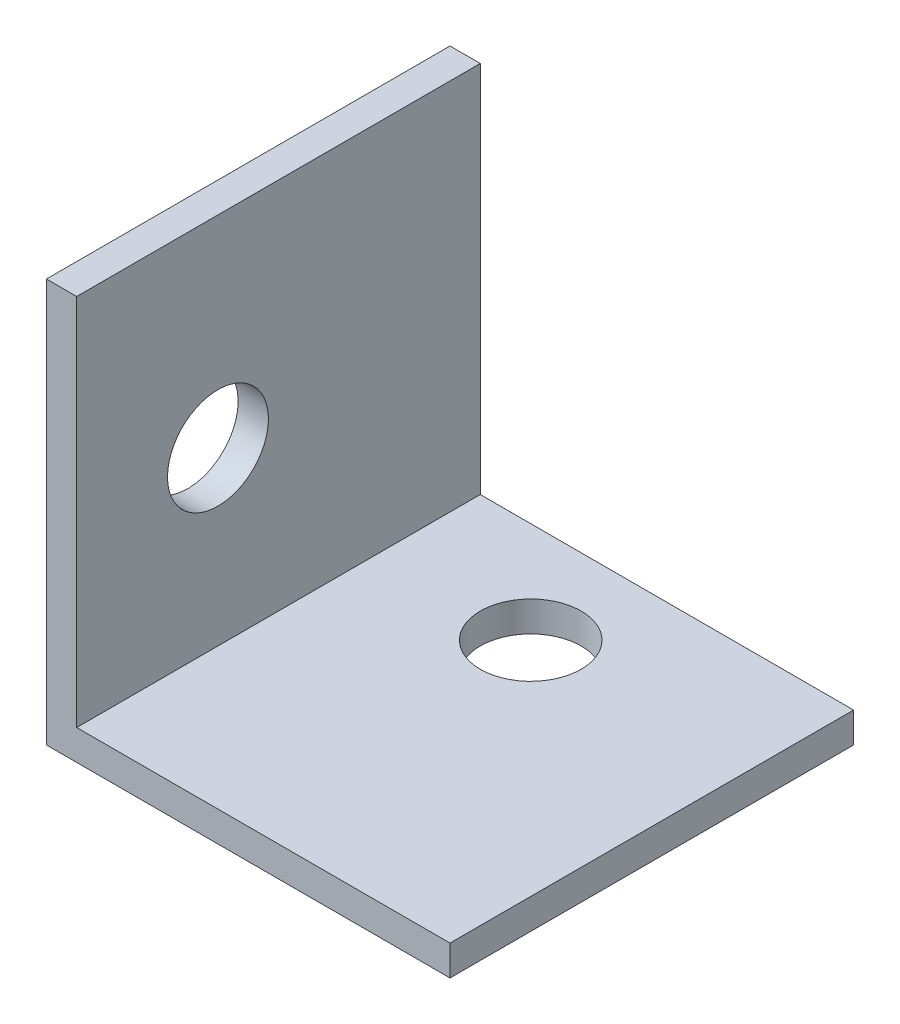
SolidWorks part; units mm, degrees
material "1060 Alloy"
ref_plane "xy" through (0, 0, 0) normal (0, 0, 1) x (1, 0, 0)
ref_plane "xz" through (0, 0, 0) normal (0, 1, 0) x (1, 0, 0)
ref_plane "yz" through (0, 0, 0) normal (1, 0, 0) x (0, 0, -1)
ref_axis "x" through (-1, 0, 0) along (1, 0, 0)
ref_axis "y" through (0, 21, 0) along (0, -1, 0)
ref_axis "z" through (0, 0, -2.575) along (0, 0, 1)
sketch "Sketch1" plane through (0, 0, 0) normal (0, 0, 1) x (1, 0, 0)
  line L0 (0, 0) -> (20, 0)
  line L1 (0, 0) -> (0, 20)
  dimension "D1" = 20
extrude "Extrude-Thin1" add sketch "Sketch1" along normal blind 20 thin thin type one direction wall 1.5
sketch "Sketch2" plane through (0, 0, 0) normal (0, -1, 0) x (-1, 0, 0)
  line L0 (-9, 0) -> (-9, -15) construction
  line L2 (-20, -20) -> (-20, 0) construction
  line L3 (-20, 0) -> (-1.5, 0) construction
  circle A0 centre (-9, -15) radius 2.5
  dimension "D2" = 5
  dimension "D1" = 15
  dimension "D3" = 11
extrude "Cut-Extrude1" cut sketch "Sketch2" against normal through all
sketch "Sketch3" plane through (1.5, 0, 0) normal (1, 0, 0) x (0, 0, -1)
  line L0 (-7, 10) -> (-7, 20) construction
  line L1 (-20, 20) -> (0, 20) construction
  line L2 (0, 1.5) -> (0, 20) construction
  circle A0 centre (-7, 10) radius 2.5
  dimension "D1" = 5
  dimension "D2" = 10
  dimension "D3" = 7
extrude "Cut-Extrude2" cut sketch "Sketch3" against normal through all
mirror "Mirror1" about plane through (0, 0, 0) normal (0, 0, 1) of bodies 103
delete or keep bodies "Body-Delete/Keep 1" type delete bodies bodies 103
